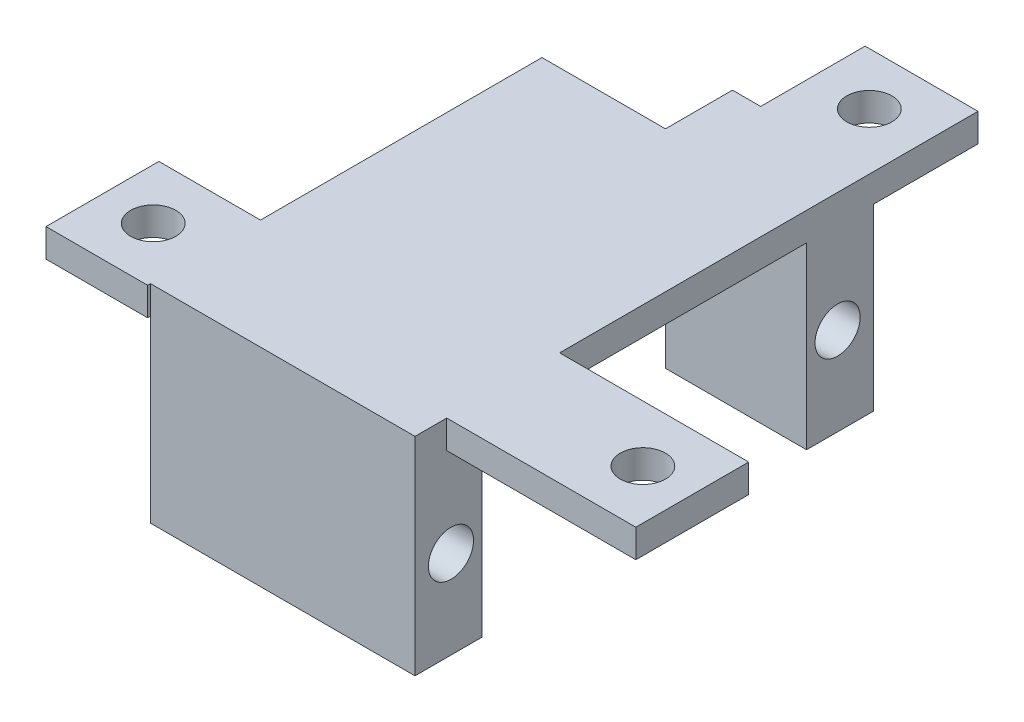
SolidWorks part; units mm, degrees
ref_plane "Front Plane" through (0, 0, 0) normal (0, 0, 1) x (1, 0, 0)
ref_plane "Top Plane" through (0, 0, 0) normal (0, 1, 0) x (1, 0, 0)
ref_plane "Right Plane" through (0, 0, 0) normal (1, 0, 0) x (0, 0, -1)
sketch "Sketch1" plane through (0, 0, 0) normal (0, 1, 0) x (1, 0, 0)
  line L0 (1.1, 16.25) -> (1.1, 11.5)
  line L1 (-17.65, -16.25) -> (17.65, -16.25)
  line L2 (-17.65, -16.25) -> (-17.65, 16.25)
  line L3 (-17.65, 16.25) -> (17.65, 16.25)
  line L4 (17.65, -16.25) -> (17.65, 16.25)
  line L5 (-17.65, -16.25) -> (17.65, 16.25) construction
  line L6 (-17.65, 16.25) -> (17.65, -16.25) construction
  line L7 (1.1, 11.5) -> (-17.65, 11.5)
  line L8 (1.1, -16.25) -> (1.1, -11.5)
  line L9 (1.1, -11.5) -> (-17.65, -11.5)
  line L10 (1.1, 11.5) -> (1.1, -11.5)
  line L11 (-8.9, 16.25) -> (-8.9, 11.5)
  line L12 (1.1, -6) -> (14.5, -6)
  line L13 (14.5, -6) -> (14.5, -14)
  line L14 (14.5, -14) -> (1.1, -14)
  line L15 (-6.9, 16.25) -> (-6.9, 23.65)
  line L16 (-6.9, 23.65) -> (1.1, 23.65)
  line L17 (1.1, 23.65) -> (1.1, 16.25)
  line L18 (-17.65, -16.45) -> (-24.85, -16.45)
  line L19 (-24.85, -16.45) -> (-24.85, -8.45)
  line L20 (-24.85, -8.45) -> (-17.65, -8.45)
  line L21 (-17.65, -16.45) -> (-17.65, -8.45)
  circle A0 centre (11, -10) radius 1.6
  circle A1 centre (-2.9, 19.95) radius 1.6
  circle A2 centre (-21.25, -12.45) radius 1.6
  point P0 (0, 0)
  point P11 (1.1, 0)
  point P36 (14.5, -10)
  point P38 (-21.25, -8.45)
  point P39 (-24.85, -12.45)
  point P41 (1.1, 19.95)
  point P42 (-2.9, 23.65)
  dimension "D6" = 3.2
  dimension "D7" = 3.2
  dimension "D8" = 3.2
  dimension "D1" = 32.5
  dimension "D2" = 23
  dimension "D3" = 8.75
  dimension "D4" = 18.75
  dimension "D5" = 16.55
  dimension "D9" = 11
  dimension "D10" = 10
  dimension "D11" = 8
  dimension "D12" = 12.45
  dimension "D13" = 8
  dimension "D14" = 21.25
  dimension "D15" = 8
  dimension "D16" = 2.9
  dimension "D17" = 19.95
  dimension "D18" = 14.5
extrude "Boss-Extrude1" add sketch "Sketch1" along normal blind 2 contours L18 L21 L2 L20 L19 A2 | A2 | L10 L7 L2 L9 | L8 L9 L2 L1 | L3 L11 L7 L0 | A1 | L17 L16 L15 L3 A1 | A0 | L14 L13 L12 L10 A0 region at (-3.9, 0, -13.875) region at (-2.9, 0, -16.359) region at (-8.275, 0, 0) region at (7.5405, 0, 10) region at (-8.275, 0, 13.875) region at (-17.7576, 0, 9.975) region at (11, 0, 10) region at (-2.9, 0, -19.95) region at (-21.25, 0, 12.45)
extrude "Boss-Extrude2" add sketch "Sketch1<5>" against normal blind 12.7 from surface contours L3 L11 L7 L0 | L8 L9 L2 L1 region at (-3.9, 0, -13.875) region at (-8.275, 0, 13.875) starting at face at (-7.4063, 0, 1.2188)
sketch "Sketch1<5>" plane through (0, 0, 0) normal (0, 1, 0) x (1, 0, 0) same geometry as "Sketch1"
extrude "Cut-Extrude1" cut sketch "Sketch1<6>" against normal through all both and the other way through all contours A1 | A0 | A2 region at (11, 0, 10) region at (-2.9, 0, -19.95) region at (-21.25, 0, 12.45)
sketch "Sketch1<6>" plane through (0, 0, 0) normal (0, 1, 0) x (1, 0, 0) same geometry as "Sketch1"
sketch "Sketch2" plane through (0, 0, 0) normal (1, 0, 0) x (0, 0, -1)
  line L0 (13.7, -6.45) -> (-13.7, -6.45) construction
  circle A0 centre (-13.7, -6.45) radius 1.6
  circle A1 centre (13.7, -6.45) radius 1.6
  point P4 (0, -6.45)
  dimension "D1" = 3.2
  dimension "D2" = 3.2
  dimension "D3" = 27.4
  dimension "D4" = 6.45
extrude "Cut-Extrude2" cut sketch "Sketch2" against normal blind 8 from surface starting at face at (1.1, -3.5667, 13.9167)
